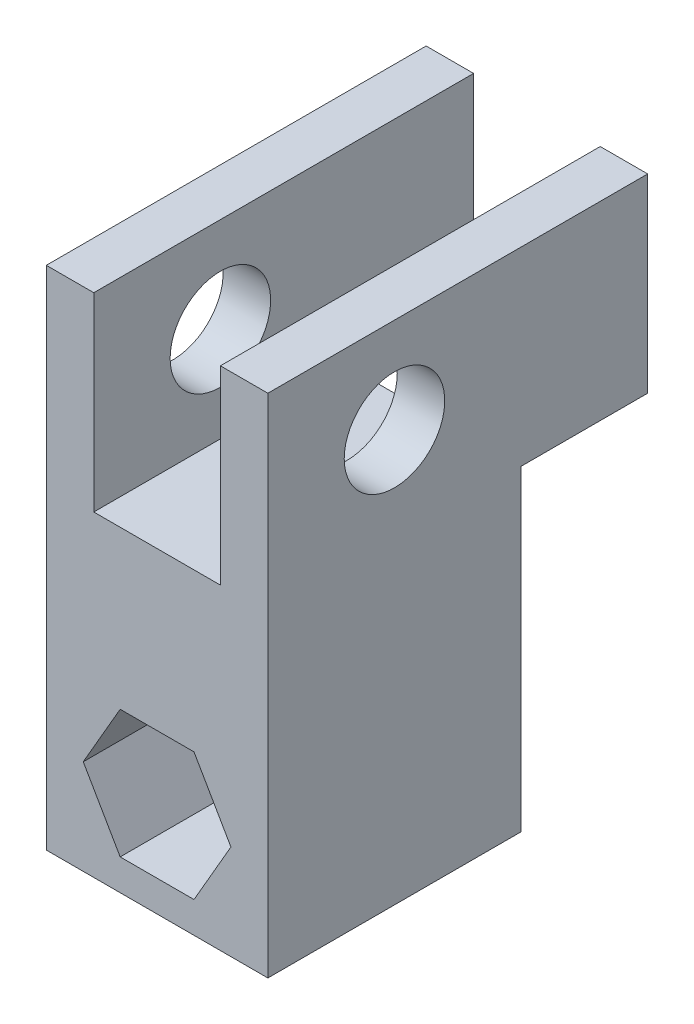
SolidWorks part; units mm, degrees
material "6061-T6 (SS)"
ref_plane "Front" through (0, 0, 0) normal (0, 0, 1) x (1, 0, 0)
ref_plane "Top" through (0, 0, 0) normal (0, 1, 0) x (1, 0, 0)
ref_plane "Right" through (0, 0, 0) normal (1, 0, 0) x (0, 0, -1)
sketch "Sketch1" plane through (0, 0, 0) normal (0, 0, 1) x (1, 0, 0)
  line L0 (-11.1125, 0) -> (11.1125, 0)
  line L1 (-11.1125, 0) -> (-11.1125, 50.8)
  line L2 (-11.1125, 50.8) -> (-6.35, 50.8)
  line L3 (-6.35, 50.8) -> (-6.35, 31.75)
  line L4 (-6.35, 31.75) -> (6.35, 31.75)
  line L5 (6.35, 31.75) -> (6.35, 50.8)
  line L6 (6.35, 50.8) -> (11.1125, 50.8)
  line L7 (11.1125, 50.8) -> (11.1125, 0)
  point P4 (0, 0)
  dimension "D1" = 22.225
  dimension "D2" = 50.8
  dimension "D3" = 12.7
  dimension "D4" = 19.05
extrude "Boss-Extrude1" add sketch "Sketch1" along normal blind 25.4
sketch "Sketch2" plane through (0, 0, 25.4) normal (0, 0, 1) x (1, 0, 0)
  line L0 (0, 0) -> (0, 3.1115) construction
  line L1 (3.7028, 15.9385) -> (-3.7028, 15.9385)
  line L2 (-3.7028, 15.9385) -> (-7.4057, 9.525)
  line L3 (-7.4057, 9.525) -> (-3.7028, 3.1115)
  line L4 (-3.7028, 3.1115) -> (3.7028, 3.1115)
  line L5 (3.7028, 3.1115) -> (7.4057, 9.525)
  line L6 (7.4057, 9.525) -> (3.7028, 15.9385)
  line L7 (-11.1125, 0) -> (11.1125, 0) construction
  circle A0 centre (0, 9.525) radius 6.4135 construction
  dimension "D1" = 12.827
  dimension "D2" = 9.525
extrude "Cut-Extrude1" cut sketch "Sketch2" against normal through all
sketch "Sketch6" plane through (-11.1125, 0, 0) normal (-1, 0, 0) x (0, 0, 1)
  line L0 (25.4, 50.8) -> (0, 50.8) construction
  line L2 (12.7, 41.275) -> (25.4, 41.275) construction
  line L3 (25.4, 50.8) -> (25.4, 0) construction
  line L5 (12.7, 41.275) -> (0, 41.275) construction
  line L6 (0, 50.8) -> (0, 0) construction
  point P0 (12.7, 41.275)
  dimension "D1" = 9.525
hole_wizard "3/8 Clearance Hole1" positions "Sketch6" profile "Sketch4" hole size "3/8" standard "ANSI Inch" end condition through all
sketch "Sketch4" plane through (-11.1125, 41.275, 12.7) normal (0, 1, 0) x (0, 0, 1)
  line L0 (0, 0) -> (0, 22.225)
  line L1 (0, 22.225) -> (5.0419, 22.225)
  line L2 (5.0419, 22.225) -> (5.0419, 0)
  line L5 (5.0419, 0) -> (0, 0)
  line L11 (0, -6.35) -> (0, 107.95) construction
  dimension "Thru Hole Dia." = 10.0838
  dimension "Thru Hole Depth" = 22.225
sketch "Sketch7" plane through (0, 0, 0) normal (0, 0, -1) x (-1, 0, 0)
  line L1 (-11.1125, 50.8) -> (-6.35, 50.8)
  line L2 (-11.1125, 50.8) -> (-11.1125, 31.75)
  line L3 (-11.1125, 31.75) -> (-6.35, 31.75)
  line L4 (-6.35, 50.8) -> (-6.35, 31.75)
  line L5 (11.1125, 50.8) -> (6.35, 50.8)
  line L6 (11.1125, 50.8) -> (11.1125, 31.75)
  line L7 (11.1125, 31.75) -> (6.35, 31.75)
  line L8 (6.35, 50.8) -> (6.35, 31.75)
extrude "Boss-Extrude2" add sketch "Sketch7" along normal blind 12.7
